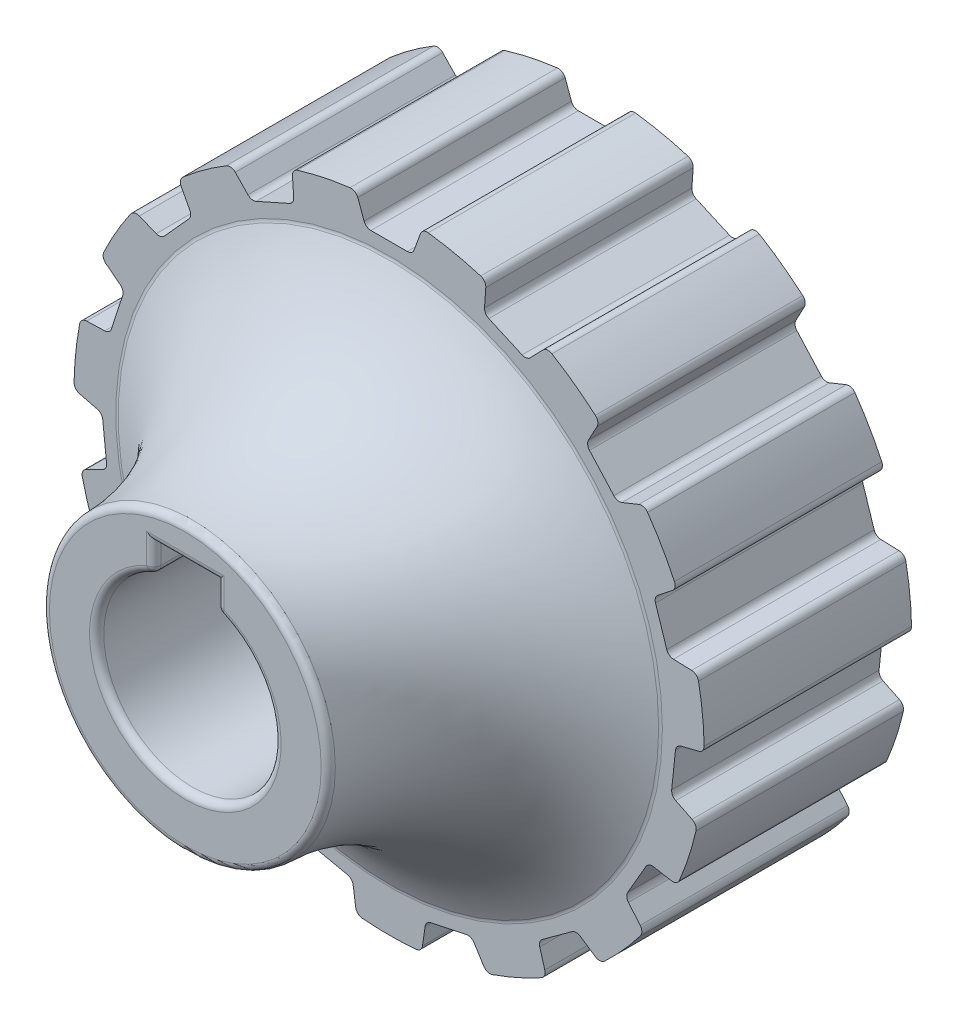
SolidWorks part; units mm, degrees
ref_plane "Front Plane" through (0, 0, 0) normal (0, 0, 1) x (1, 0, 0)
ref_plane "Top Plane" through (0, 0, 0) normal (0, 1, 0) x (1, 0, 0)
ref_plane "Right Plane" through (0, 0, 0) normal (1, 0, 0) x (0, 0, -1)
sketch "Sketch1" plane through (0, 0, 0) normal (0, 1, 0) x (1, 0, 0)
  line L0 (0, 36.1296) -> (0, -19.4741) construction
sketch "Sketch7" plane through (0, 0, 0) normal (0, 0, 1) x (1, 0, 0)
  line L0 (0, 0) -> (0, 20.9536) construction
  line L1 (-2.325, 21.9086) -> (-2.9401, 23.5986) construction
  line L2 (-2.325, 21.9086) -> (-1.6298, 19.9986) construction
  line L3 (-1.6298, 19.9986) -> (1.6298, 19.9986) construction
  line L4 (1.6298, 19.9986) -> (2.325, 21.9086) construction
  line L5 (2.325, 21.9086) -> (-2.325, 21.9086) construction
  line L6 (0, 19.9986) -> (0, 21.9086) construction
  line L7 (2.325, 21.9086) -> (2.9401, 23.5986) construction
  line L8 (-2.9401, 23.5986) -> (2.9401, 23.5986) construction
  line L9 (0, 0) -> (8.5226, 19.1421) construction
  line L10 (8.5226, 19.1421) -> (8.9611, 20.1269) construction
  line L11 (0, 21.9086) -> (0, 22.0316) construction
  line L12 (0, 22.0316) -> (0, 23.7811) construction
  line L13 (0, 22.9064) -> (9.3169, 20.926) construction
  line L14 (8.9611, 20.1269) -> (9.6726, 21.7251) construction
  circle A1 centre (0, 0) radius 20.9536 construction
  circle A2 centre (-1.2727, 20.5086) radius 0.51 construction
  circle A3 centre (1.2727, 20.5086) radius 0.51 construction
  circle A4 centre (0, 0) radius 22.0316
  circle A5 centre (0, 0) radius 23.7811 construction
  dimension "D3" = 40
  dimension "D6" = 1.02
  dimension "D1" = 3.6
  dimension "D2" = 24
  dimension "D7" = 9.525
  dimension "D4" = 1.91
  dimension "D5" = 4.65
extrude "Boss-Extrude1" add sketch "Sketch7" along normal blind 7.25 and the other way blind 7.25 contours A4 region at (0, 0, 0)
sketch "Sketch14" plane through (0, 0, 0) normal (1, 0, 0) x (0, 0, -1)
  line L0 (-21.5, 0) -> (-21.5, 10)
  line L1 (-21.5, 0) -> (0, 0)
  line L2 (0, 0) -> (0, 19)
  line L3 (0, 19) -> (-7.25, 19)
  line L4 (-7.25, 19) -> (-21.5, 10)
  line L5 (-7.25, 22.0316) -> (-7.25, -22.0316) construction
  line L6 (-21.5, 7.0431) -> (-2.5683, 19) construction
  arc A0 (-7.25, 19) -> (-21.5, 10) centre (-21.2919, 25.4517) cw
  dimension "D1" = 10
  dimension "D2" = 19
  dimension "D3" = 21.5
  dimension "D4" = 2.5
revolve "Revolve1" add sketch "Sketch14" angle 360 about L0 region at (0, 7.3866, 9.0486) region at (0, 9.3218, 19.3148) region at (0, 17.2024, 6.8722)
sketch "Sketch8" plane through (0, 0, 0) normal (0, 0, 1) x (1, 0, 0)
  line L6 (-1.6298, 19.9986) -> (-2.3698, 22.0316)
  line L7 (-2.3698, 22.0316) -> (2.3698, 22.0316)
  line L8 (2.3698, 22.0316) -> (1.6298, 19.9986)
  line L9 (1.6298, 19.9986) -> (-1.6298, 19.9986)
  line L10 (-2.325, 21.9086) -> (-1.6298, 19.9986) construction
  line L11 (1.6298, 19.9986) -> (2.325, 21.9086) construction
  line L12 (6.6453, 18.9326) -> (6.7962, 21.0908)
  line L13 (6.7962, 21.0908) -> (11.126, 19.163)
  line L14 (11.126, 19.163) -> (9.6231, 17.6067)
  line L15 (9.6231, 17.6067) -> (6.6453, 18.9326)
  line L16 (13.7713, 14.5929) -> (14.787, 16.5031)
  line L17 (14.787, 16.5031) -> (17.9584, 12.981)
  line L18 (17.9584, 12.981) -> (15.9524, 12.1705)
  line L19 (15.9524, 12.1705) -> (13.7713, 14.5929)
  line L20 (18.5162, 7.73) -> (20.221, 9.0619)
  line L21 (20.221, 9.0619) -> (21.6856, 4.5544)
  line L22 (21.6856, 4.5544) -> (19.5235, 4.6299)
  line L23 (19.5235, 4.6299) -> (18.5162, 7.73)
  line L24 (20.0594, -0.4695) -> (22.1587, 0.0539)
  line L25 (22.1587, 0.0539) -> (21.6632, -4.6597)
  line L26 (21.6632, -4.6597) -> (19.7187, -3.7113)
  line L27 (19.7187, -3.7113) -> (20.0594, -0.4695)
  line L28 (18.1342, -8.5879) -> (20.2649, -8.9635)
  line L29 (20.2649, -8.9635) -> (17.8951, -13.0681)
  line L30 (17.8951, -13.0681) -> (16.5044, -11.4108)
  line L31 (16.5044, -11.4108) -> (18.1342, -8.5879)
  line L32 (13.0734, -15.2212) -> (14.8671, -16.4311)
  line L33 (14.8671, -16.4311) -> (11.0327, -19.2169)
  line L34 (11.0327, -19.2169) -> (10.4363, -17.1372)
  line L35 (10.4363, -17.1372) -> (13.0734, -15.2212)
  line L36 (5.7521, -19.2227) -> (6.8986, -21.0575)
  line L37 (6.8986, -21.0575) -> (2.2626, -22.0429)
  line L38 (2.2626, -22.0429) -> (2.5637, -19.9005)
  line L39 (2.5637, -19.9005) -> (5.7521, -19.2227)
  line L40 (-2.5637, -19.9005) -> (-2.2626, -22.0429)
  line L41 (-2.2626, -22.0429) -> (-6.8986, -21.0575)
  line L42 (-6.8986, -21.0575) -> (-5.7521, -19.2227)
  line L43 (-5.7521, -19.2227) -> (-2.5637, -19.9005)
  line L44 (-10.4363, -17.1372) -> (-11.0327, -19.2169)
  line L45 (-11.0327, -19.2169) -> (-14.8671, -16.4311)
  line L46 (-14.8671, -16.4311) -> (-13.0734, -15.2212)
  line L47 (-13.0734, -15.2212) -> (-10.4363, -17.1372)
  line L48 (-16.5044, -11.4108) -> (-17.8951, -13.0681)
  line L49 (-17.8951, -13.0681) -> (-20.2649, -8.9635)
  line L50 (-20.2649, -8.9635) -> (-18.1342, -8.5879)
  line L51 (-18.1342, -8.5879) -> (-16.5044, -11.4108)
  line L52 (-19.7187, -3.7113) -> (-21.6632, -4.6597)
  line L53 (-21.6632, -4.6597) -> (-22.1587, 0.0539)
  line L54 (-22.1587, 0.0539) -> (-20.0594, -0.4695)
  line L55 (-20.0594, -0.4695) -> (-19.7187, -3.7113)
  line L56 (-19.5235, 4.6299) -> (-21.6856, 4.5544)
  line L57 (-21.6856, 4.5544) -> (-20.221, 9.0619)
  line L58 (-20.221, 9.0619) -> (-18.5162, 7.73)
  line L59 (-18.5162, 7.73) -> (-19.5235, 4.6299)
  line L60 (-15.9524, 12.1705) -> (-17.9584, 12.981)
  line L61 (-17.9584, 12.981) -> (-14.787, 16.5031)
  line L62 (-14.787, 16.5031) -> (-13.7713, 14.5929)
  line L63 (-13.7713, 14.5929) -> (-15.9524, 12.1705)
  line L64 (-9.6231, 17.6067) -> (-11.126, 19.163)
  line L65 (-11.126, 19.163) -> (-6.7962, 21.0908)
  line L66 (-6.7962, 21.0908) -> (-6.6453, 18.9326)
  line L67 (-6.6453, 18.9326) -> (-9.6231, 17.6067)
  circle A0 centre (0, 0) radius 22.0316 construction
  point P119 (0, 0)
  dimension "D1" = 15
extrude "Cut-Extrude2" cut sketch "Sketch8" against normal through all both and the other way through all
fillet "Fillet2" radius 0.51 60 edges at (-6.787, 20.9602, 0) (-11.035, 19.0689, 0) (-14.7256, 16.3875, 0) (-17.837, 12.9319, 0) (-20.1179, 8.9813, 0) (-21.5548, 4.5589, 0) (-22.0316, 0.0222, 0) (-21.5456, -4.6023, 0) (-20.1359, -8.9408, 0) (-17.8109, -12.9678, 0) (-14.7585, -16.3578, 0) (-10.9966, -19.0911, 0) (-6.8293, -20.9465, 0) (-2.2809, -21.9133, 0) (2.2809, -21.9133, 0) (6.8293, -20.9465, 0) (10.9966, -19.0911, 0) (14.7585, -16.3578, 0) (17.8109, -12.9678, 0) (20.1359, -8.9408, 0) (21.5456, -4.6023, 0) (22.0316, 0.0222, 0) (21.5548, 4.5589, 0) (20.1179, 8.9813, 0) (17.837, 12.9319, 0) (14.7256, 16.3875, 0) (11.035, 19.0689, 0) (6.787, 20.9602, 0) (2.325, 21.9086, 0) (-6.6453, 18.9326, 0) (-9.6231, 17.6067, 0) (-13.7713, 14.5929, 0) (-15.9524, 12.1705, 0) (-18.5162, 7.73, 0) (-19.5235, 4.6299, 0) (-20.0594, -0.4695, 0) (-19.7187, -3.7113, 0) (-18.1342, -8.5879, 0) (-16.5044, -11.4108, 0) (-13.0734, -15.2212, 0) (-10.4363, -17.1372, 0) (-5.7521, -19.2227, 0) (-2.5637, -19.9005, 0) (2.5637, -19.9005, 0) (5.7521, -19.2227, 0) (10.4363, -17.1372, 0) (13.0734, -15.2212, 0) (16.5044, -11.4108, 0) (18.1342, -8.5879, 0) (19.7187, -3.7113, 0) (20.0594, -0.4695, 0) (19.5235, 4.6299, 0) (18.5162, 7.73, 0) (15.9524, 12.1705, 0) (13.7713, 14.5929, 0) (9.6231, 17.6067, 0) (6.6453, 18.9326, 0) (1.6298, 19.9986, 0) (-1.6298, 19.9986, 0) (-2.325, 21.9086, 0)
sketch "Sketch9" plane through (0, 0, 0) normal (0, 0, 1) x (1, 0, 0)
  line L0 (2, 0) -> (-2, 0) construction
  line L1 (-2, 0) -> (-2, 7.5) construction
  line L2 (-2, 7.5) -> (2, 7.5) construction
  line L3 (2, 7.5) -> (2, 0) construction
  circle A0 centre (0, 0) radius 6 construction
  dimension "D1" = 12
  dimension "D2" = 4
  dimension "D3" = 7.5
sketch "Sketch10" plane through (0, 0, 0) normal (0, 0, 1) x (1, 0, 0)
  line L0 (2, 0) -> (-2, 0) construction
  line L1 (-2.2, 7.7) -> (2.2, 7.7)
  line L2 (-2.2, 7.7) -> (-2.2, 0)
  line L3 (-2.2, 0) -> (2.2, 0)
  line L4 (2.2, 7.7) -> (2.2, 0)
  line L5 (-2, 7.5) -> (2, 7.5) construction
  line L6 (2, 7.5) -> (2, 0) construction
  circle A0 centre (0, 0) radius 6.2
  circle A1 centre (0, 0) radius 6 construction
  dimension "D1" = 0.2
  dimension "D2" = 0.2
  dimension "D3" = 0.2
extrude "Cut-Extrude3" cut sketch "Sketch10" against normal through all both and the other way through all contours A0 L4 L1 L2 | L2 A0 L4 L3 | L4 A0 L2 L3 region at (0, 6.8793, 0) region at (0, 3.0348, 0) region at (0, -0.8613, 0)
sketch "Sketch11" plane through (0, 0, 0) normal (0, 1, 0) x (1, 0, 0)
  line L0 (10.6417, 7.25) -> (7.2154, 7.25) construction
  line L1 (11, 7.25) -> (17.5, 7.25)
  line L2 (11, 7.25) -> (11, 4.75)
  line L3 (11, 4.75) -> (17.5, 4.75)
  line L4 (17.5, 7.25) -> (17.5, 4.75)
  line L5 (7.2154, -7.25) -> (10.6417, -7.25) construction
  line L6 (11, -7.25) -> (17.5, -7.25)
  line L7 (11, -7.25) -> (11, -4.75)
  line L8 (11, -4.75) -> (17.5, -4.75)
  line L9 (17.5, -7.25) -> (17.5, -4.75)
  line L11 (11, 4.75) -> (11, -4.75) construction
  line L12 (17.5, -4.75) -> (17.5, 4.75) construction
  line L13 (6.2, 7.25) -> (-6.2, 7.25) construction
  line L14 (0, 7.25) -> (22.5, 7.25)
  line L15 (0, 7.25) -> (0, -7.25)
  line L16 (0, -7.25) -> (22.5, -7.25)
  line L17 (22.5, 7.25) -> (22.5, -7.25)
  line L18 (-6.2, -7.25) -> (6.2, -7.25) construction
  line L19 (6, 7.25) -> (6, -7.25) construction
  dimension "D1" = 22.5
  dimension "D2" = 6
  dimension "D3" = 5
  dimension "D4" = 5
  dimension "D5" = 2.5
revolve "Cut-Revolve1" [suppressed] cut sketch "Sketch11" angle 360 about L0
sketch "Sketch15" plane through (0, 0, -7.25) normal (0, 0, -1) x (-1, 0, 0)
  circle A0 centre (0, 0) radius 8.0081
  circle A1 centre (0, 0) radius 2.25
  dimension "D1" = 4.5
extrude "Boss-Extrude2" add sketch "Sketch15" against normal blind 5.5
sketch "Sketch16" plane through (0, 0, -7.25) normal (0, 0, -1) x (-1, 0, 0)
  circle A0 centre (0, 0) radius 5
  dimension "D1" = 10
extrude "Cut-Extrude4" cut sketch "Sketch16" against normal blind 3
fillet "Fillet3" radius 0.5 11 edges at (2.2, 5.7966, 9.875) (-2.2, 5.7966, 9.875) (2.2, 6.7483, 21.5) (-2.2, 6.7483, 21.5) (0, 7.7, 21.5) (-19, 0, 7.25) (-10, 0, 21.5) (0, -6.2, 21.5) (-5, 0, -7.25) (-5, 0, -4.25) (-2.25, 0, -4.25)
